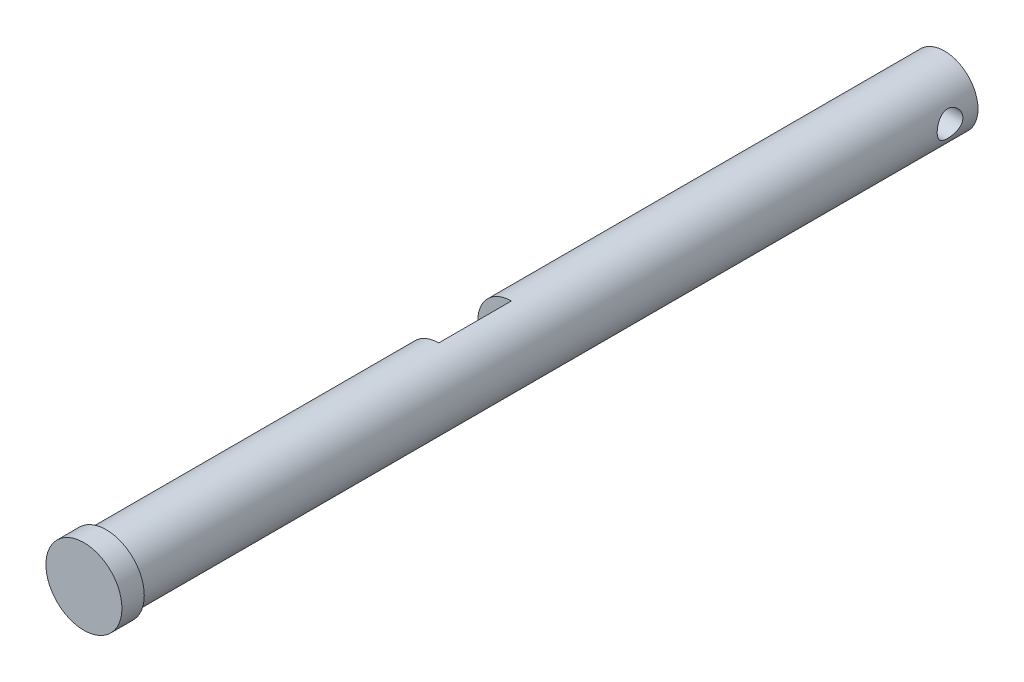
SolidWorks part; units mm, degrees
material "Alliage de zinc AC41A, brut"
ref_plane "Plan de face" through (0, 0, 0) normal (0, 0, 1) x (1, 0, 0)
ref_plane "Plan de dessus" through (0, 0, 0) normal (0, 1, 0) x (1, 0, 0)
ref_plane "Plan de droite" through (0, 0, 0) normal (1, 0, 0) x (0, 0, -1)
sketch "Sketch1" plane through (0, 0, 0) normal (0, 0, 1) x (1, 0, 0)
  circle A0 centre (0, 0) radius 3
  dimension "D1" = 6
extrude "Boss-Extrude1" add sketch "Sketch1" along normal blind 38.75
sketch "Sketch2" plane through (0, 0, 38.75) normal (0, 0, 1) x (1, 0, 0)
  line L0 (0, 3) -> (0, -3)
  arc A0 (0, -3) -> (0, 3) centre (0, 0) ccw
  point P5 (0, 3)
  dimension "D1" = 6
extrude "Boss-Extrude2" add sketch "Sketch2" along normal blind 6.5
sketch "Sketch3" plane through (0, 0, 45.25) normal (0, 0, 1) x (1, 0, 0)
  circle A0 centre (0, 0) radius 3
  dimension "D1" = 6
extrude "Boss-Extrude3" add sketch "Sketch3" along normal blind 29.75
sketch "Sketch4" plane through (0, 0, 75) normal (0, 0, 1) x (1, 0, 0)
  circle A0 centre (0, 0) radius 3.4
  dimension "D1" = 6.8
extrude "Boss-Extrude4" add sketch "Sketch4" along normal blind 2
sketch "Sketch5" plane through (0, 0, 0) normal (1, 0, 0) x (0, 0, -1)
  line L0 (0, 0) -> (-2.5, 0) construction
  circle A0 centre (-2.5, 0) radius 1.15
  dimension "D2" = 2.3
  dimension "D1" = 2.5
extrude "Cut-Extrude1" cut sketch "Sketch5" against normal up to next and the other way up to next
